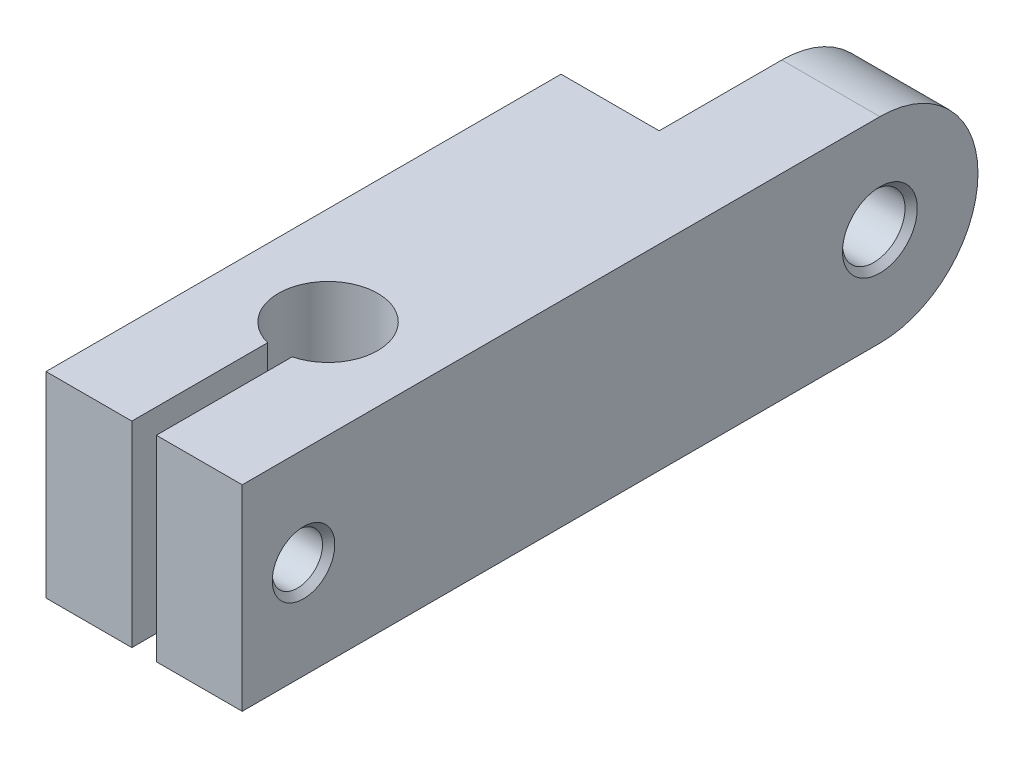
SolidWorks part; units mm, degrees
material "6063-T6"
ref_plane "Front Plane" through (0, 0, 0) normal (0, 0, 1) x (1, 0, 0)
ref_plane "Top Plane" through (0, 0, 0) normal (0, 1, 0) x (1, 0, 0)
ref_plane "Right Plane" through (0, 0, 0) normal (1, 0, 0) x (0, 0, -1)
sketch "Sketch1" plane through (0, 0, 0) normal (0, 0, 1) x (1, 0, 0)
  line L1 (8, -8) -> (-8, -8)
  line L2 (8, -8) -> (8, 8)
  line L3 (8, 8) -> (-8, 8)
  line L4 (-8, -8) -> (-8, 8)
  line L5 (8, -8) -> (-8, 8) construction
  line L6 (8, 8) -> (-8, -8) construction
  point P0 (0, 0)
extrude "Base" add sketch "Sketch1" along normal blind 60
sketch "Sketch2" plane through (0, 8, 0) normal (0, 1, 0) x (1, 0, 0)
  line L0 (-1, -60) -> (-1, -48.9246)
  line L1 (8, -60) -> (-8, -60) construction
  line L2 (1, -60) -> (1, -48.9246)
  line L3 (0, 0) -> (0, -9.2456) construction
  circle A0 centre (0, -45) radius 4.05
  line M6 (-8, -60) -> (8, -60)
  dimension "D1" = 8.1
  dimension "D2" = 15
  dimension "D3" = 2
extrude "IndicatorHole" cut sketch "Sketch2" against normal through all contours A0 | A0 L0 L2 M6 region at (0, 8, 54.5042) region at (0, 8, 45)
sketch "Sketch3" plane through (8, 0, 0) normal (1, 0, 0) x (0, 0, -1)
  line L0 (-60, -8) -> (-60, 8) construction
  circle A0 centre (-55, 0) radius 2.05
  dimension "D1" = 4.1
  dimension "D2" = 5
extrude "IndicatorMount" cut sketch "Sketch3" against normal up to next
chamfer "ChamferIndicatorMount" distance 0.5 angle 45 1 edges at (8, 0, 52.95)
hole_wizard "M4x0.7 Tapped Hole for IndicatorScrew" positions "Sketch4" profile "Sketch5" tap size "M4x0.7" standard "ANSI Metric"
sketch "Sketch4" plane through (-8, 0, 0) normal (-1, 0, 0) x (0, 0, 1)
  point P0 (55, 0)
cosmetic thread "Hole Thread1" parameters "D1"=7, "D2"=4
sketch "Sketch5" plane through (-8, 0, 55) normal (0, 1, 0) x (0, 0, 1)
  line L0 (0, 0) -> (0, 8.9)
  line L1 (0, 8.9) -> (1.65, 7.9086)
  line L2 (1.65, 7.9086) -> (1.65, 0)
  line L5 (1.65, 0) -> (0, 0)
  line L10 (0, 8.9) -> (-1.65, 7.9086) construction
  line L11 (0, -6.35) -> (0, 107.95) construction
  dimension "Tap Drill Dia." = 3.3
  dimension "Tap Drill Depth" = 8.9
  dimension "Drill Angle" = 118
sketch "Sketch6" plane through (0, 0, 0) normal (1, 0, 0) x (0, 0, -1)
  line L0 (-60, -8) -> (0, -8) construction
  line L1 (-18, 8) -> (1.869, 8)
  line L2 (-18, 8) -> (-18, -8)
  line L3 (-18, -8) -> (1.869, -8)
  line L4 (1.869, 8) -> (1.869, -8)
  line L5 (-60, 8) -> (0, 8) construction
  line L6 (0, -8) -> (0, 8) construction
  circle A0 centre (-8, 0) radius 8
  dimension "D2" = 8
  dimension "D1" = 18
extrude "SlotForAnotherPart" cut sketch "Sketch6" against normal through all contours A0 L1 L2 L3 | A0 | A0 L3 L4 L1 region at (0, 7.8113, 13) region at (0, 7.812, 3.0655) region at (0, 0, 8)
extrude "ChamferForSlot" cut sketch "Sketch6<3>" along normal through all contours A0 L3 L4 L1 region at (0, 7.812, 3.0655)
sketch "Sketch6<3>" plane through (0, 0, 0) normal (1, 0, 0) x (0, 0, -1) same geometry as "Sketch6"
sketch "Sketch7" plane through (8, 0, 0) normal (1, 0, 0) x (0, 0, -1)
  circle A0 centre (-8, 0) radius 2.55
  dimension "D1" = 5.1
extrude "ScrewHoleForSlot" cut sketch "Sketch7" against normal through all
chamfer "ChamferForScrewSlot" distance 0.5 angle 45 1 edges at (8, 0, 5.45)
equation "\"D2@Sketch1\"=\"D1@Sketch1\""
